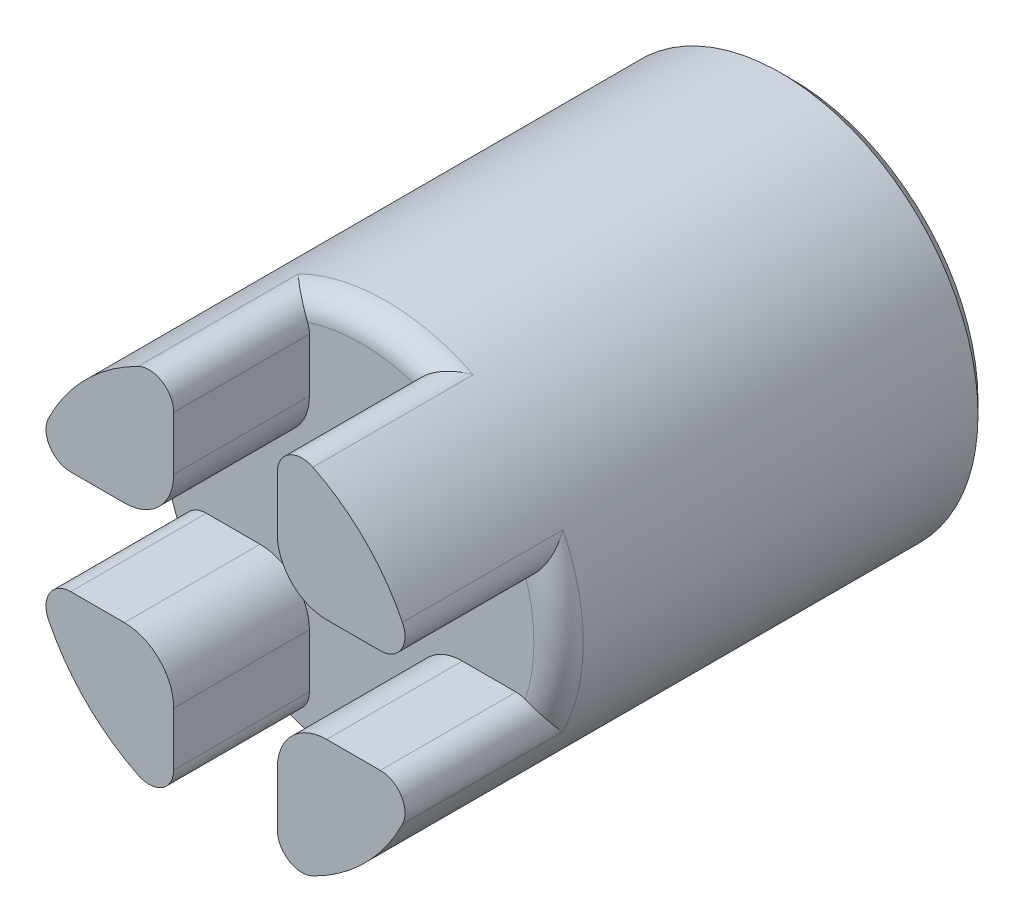
SolidWorks part; units mm, degrees
ref_plane "Front Plane" through (0, 0, 0) normal (0, 0, 1) x (1, 0, 0)
ref_plane "Top Plane" through (0, 0, 0) normal (0, 1, 0) x (1, 0, 0)
ref_plane "Right Plane" through (0, 0, 0) normal (1, 0, 0) x (0, 0, -1)
sketch "Sketch1" plane through (0, 0, 0) normal (0, 0, 1) x (1, 0, 0)
  line L0 (-1.3, 1.6492) -> (-1.3, -1.6492)
  circle A0 centre (0, 0) radius 8
  arc A1 (-1.3, -1.6492) -> (-1.3, 1.6492) centre (0, 0) ccw
  dimension "D1" = 4.2
  dimension "D2" = 16
  dimension "D3" = 1.3
extrude "Boss-Extrude1" add sketch "Sketch1" along normal blind 23
sketch "Sketch2" plane through (0, 0, 23) normal (0, 0, 1) x (1, 0, 0)
  line L0 (4.1, 2.1) -> (9.8748, 2.1)
  line L1 (-9.8748, 2.1) -> (-4.1, 2.1)
  line L2 (-9.8748, 2.1) -> (-9.8748, -2.1)
  line L3 (-9.8748, -2.1) -> (-4.1, -2.1)
  line L4 (9.8748, 2.1) -> (9.8748, -2.1)
  line L5 (-9.8748, 2.1) -> (9.8748, -2.1) construction
  line L6 (-9.8748, -2.1) -> (9.8748, 2.1) construction
  line L7 (-2.1, 8.2699) -> (2.1, 8.2699)
  line L8 (-2.1, 8.2699) -> (-2.1, 4.1)
  line L9 (-2.1, -8.2699) -> (2.1, -8.2699)
  line L10 (2.1, 8.2699) -> (2.1, 4.1)
  line L11 (-2.1, 8.2699) -> (2.1, -8.2699) construction
  line L12 (-2.1, -8.2699) -> (2.1, 8.2699) construction
  line L13 (-2.1, -4.1) -> (-2.1, -8.2699)
  line L15 (2.1, -4.1) -> (2.1, -8.2699)
  line L16 (4.1, -2.1) -> (9.8748, -2.1)
  arc A0 (-2.1, -4.1) -> (-4.1, -2.1) centre (-4.1, -4.1) ccw
  arc A1 (-4.1, 2.1) -> (-2.1, 4.1) centre (-4.1, 4.1) ccw
  arc A2 (4.1, 2.1) -> (2.1, 4.1) centre (4.1, 4.1) cw
  arc A3 (2.1, -4.1) -> (4.1, -2.1) centre (4.1, -4.1) cw
  point P0 (0, 0)
  point P6 (0, 0)
  point P23 (2.1, -2.1)
  dimension "D3" = 2
  dimension "D1" = 4.2
  dimension "D2" = 4.2
extrude "Cut-Extrude1" cut sketch "Sketch2" against normal blind 5.5
chamfer "Chamfer1" distance 0.5 angle 45 1 edges at (8, 0, 0)
fillet "Fillet1" radius 1 10 edges at (-7.7195, 2.1, 20.25) (-7.7195, -2.1, 20.25) (-2.1, -7.7195, 20.25) (2.1, -7.7195, 20.25) (7.7195, -2.1, 20.25) (8, 0, 17.5) (7.7195, 2.1, 20.25) (2.1, 7.7195, 20.25) (0, 8, 17.5) (-2.1, 7.7195, 20.25)
sketch "Sketch3" plane through (-1.3, 0, 0) normal (1, 0, 0) x (0, 0, -1)
  circle A0 centre (-7.3438, 0) radius 2.75
  dimension "D1" = 5.5
extrude "Cut-Extrude2" cut sketch "Sketch3" against normal blind 15.5
sketch "Sketch5" plane through (-1.3, 0, 0) normal (1, 0, 0) x (0, 0, -1)
  circle A0 centre (-7.3438, 0) radius 3.2398
  circle A1 centre (-7.3438, 0) radius 1.3
  dimension "D1" = 2.6
extrude "Boss-Extrude2" add sketch "Sketch5" against normal blind 4
